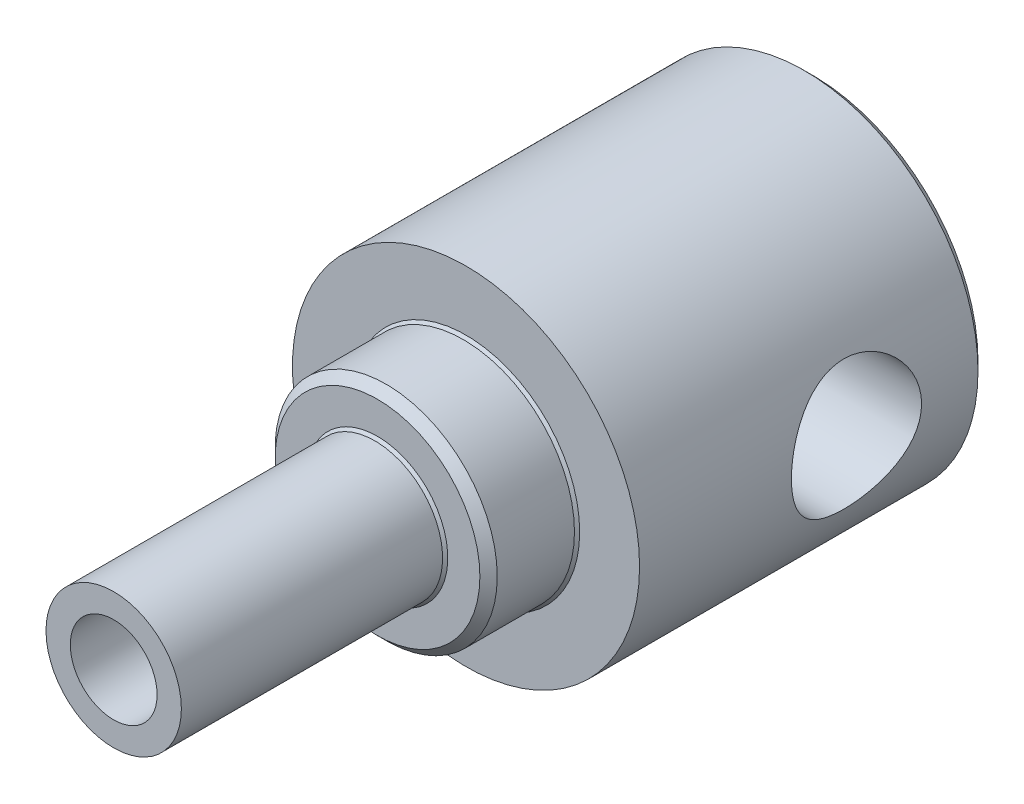
SolidWorks part; units mm, degrees
ref_plane "Front Plane" through (0, 0, 0) normal (0, 0, 1) x (1, 0, 0)
ref_plane "Top Plane" through (0, 0, 0) normal (0, 1, 0) x (1, 0, 0)
ref_plane "Right Plane" through (0, 0, 0) normal (1, 0, 0) x (0, 0, -1)
sketch "Sketch1" plane through (0, 0, 0) normal (0, 0, 1) x (1, 0, 0)
  circle A0 centre (0, 0) radius 1
  dimension "D1" = 2
extrude "Boss-Extrude1" add sketch "Sketch1" against normal blind 2
sketch "Sketch2" plane through (0, 0, 0) normal (0, 0, 1) x (1, 0, 0)
  circle A0 centre (0, 0) radius 0.64
  dimension "D1" = 1.28
extrude "Boss-Extrude2" add sketch "Sketch2" along normal blind 0.51
sketch "Sketch3" plane through (0, 0, 0.51) normal (0, 0, 1) x (1, 0, 0)
  circle A0 centre (0, 0) radius 0.39
  dimension "D1" = 0.78
extrude "Boss-Extrude3" add sketch "Sketch3" along normal blind 1.52
chamfer "Chamfer1" distance 0.05 angle 45 2 edges at (0.64, 0, 0.51) (1, 0, -2)
ref_plane "Plane1" through (1, 0, 0) normal (1, 0, 0) x (0, 0, -1)
sketch "Sketch4" plane through (1, 0, 0) normal (1, 0, 0) x (0, 0, -1)
  line L1 (2, -0.95) -> (2, 0.95) construction
  circle A0 centre (1.25, 0) radius 0.375
  dimension "D2" = 0.75
  dimension "D1" = 0.75
  dimension "D3" = 1.25
extrude "Cut-Extrude1" cut sketch "Sketch4" against normal through all
chamfer "Chamfer2" distance 0.015 angle 45 1 edges at (0.64, 0, 0)
ref_plane "Plane2" through (-0.39, 0, 0) normal (-1, 0, 0) x (0, 0, 1)
sketch "Sketch5" plane through (-0.39, 0, 0) normal (-1, 0, 0) x (0, 0, 1)
  line L0 (0.51, 0) -> (2.03, 0) construction
  line L1 (0.51, -0.39) -> (0.51, 0.39) construction
  line L2 (2.03, -0.39) -> (2.03, 0.39) construction
  line L3 (1.41, 0) -> (0.6, 0) construction
  line L4 (1.41, -0.09) -> (0.6, -0.09)
  line L5 (1.41, 0.09) -> (0.6, 0.09)
  line L6 (0.51, -0.59) -> (0.51, 0.59) construction
  arc A0 (1.41, -0.09) -> (1.41, 0.09) centre (1.41, 0) ccw
  arc A1 (0.6, 0.09) -> (0.6, -0.09) centre (0.6, 0) ccw
  point P8 (1.005, 0)
  dimension "D2" = 0.09
  dimension "D1" = 0.09
  dimension "D3" = 0.81
extrude "Cut-Extrude2" cut sketch "Sketch5" against normal blind 0.0938 and the other way blind 0.0938
chamfer "Chamfer3" distance 0.015 angle 45 1 edges at (0.39, 0, 0.51)
sketch "Sketch9" plane through (0, 0, 2.03) normal (0, 0, 1) x (1, 0, 0)
  circle A0 centre (0, 0) radius 0.25
  dimension "D1" = 0.5
extrude "Cut-Extrude3" cut sketch "Sketch9" against normal blind 0.75
